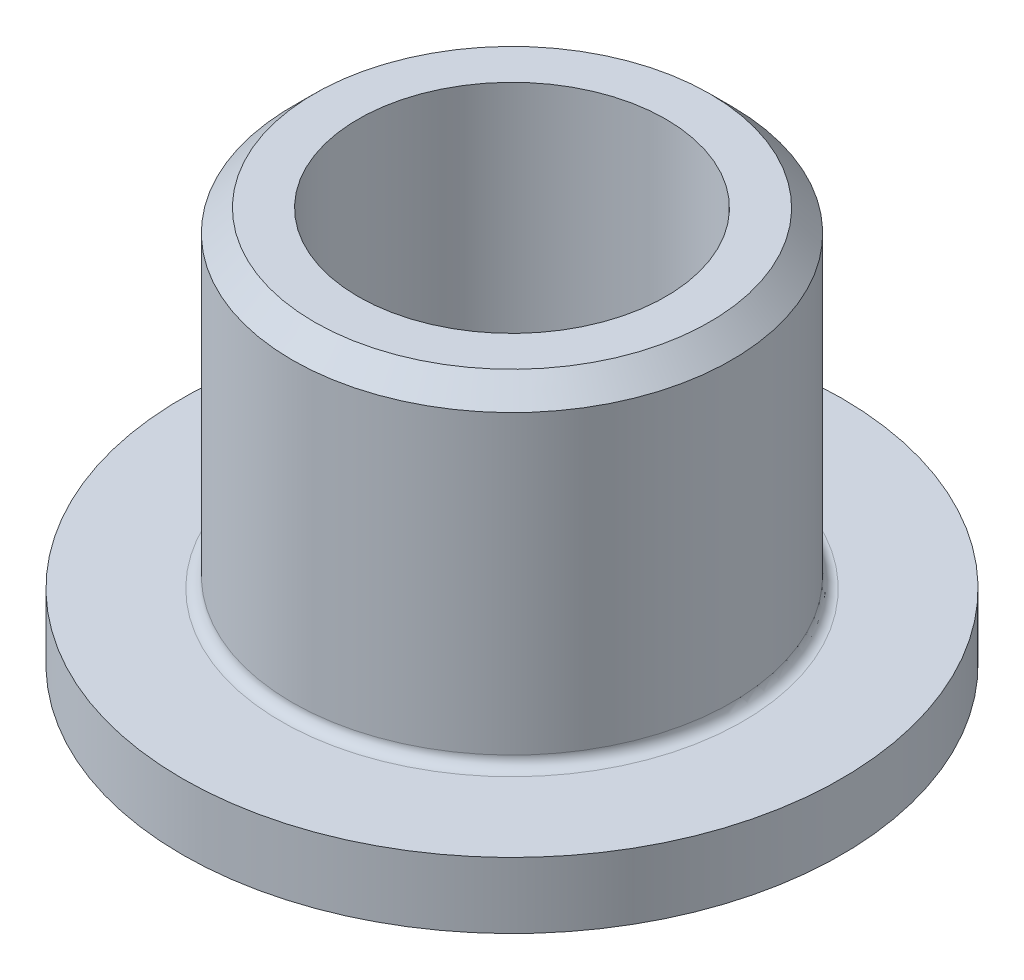
SolidWorks part; units mm, degrees
material "PTFE (general)"
ref_plane "Front Plane" through (0, 0, 0) normal (0, 0, 1) x (1, 0, 0)
ref_plane "Top Plane" through (0, 0, 0) normal (0, 1, 0) x (1, 0, 0)
ref_plane "Right Plane" through (0, 0, 0) normal (1, 0, 0) x (0, 0, -1)
sketch "Sketch1" plane through (0, 0, 0) normal (0, 1, 0) x (1, 0, 0)
  circle A0 centre (0, 0) radius 3.5
  circle A1 centre (0, 0) radius 5
  dimension "D1" = 7
  dimension "D2" = 1.5
extrude "Boss-Extrude1" add sketch "Sketch1" along normal blind 7.5
sketch "Sketch2" plane through (0, 0, 0) normal (0, -1, 0) x (1, 0, 0)
  circle A0 centre (0, 0) radius 3.5 construction
  circle A1 centre (0, 0) radius 3.5
  circle A2 centre (0, 0) radius 5 construction
  circle A3 centre (0, 0) radius 5 construction
  circle A4 centre (0, 0) radius 7.5
  dimension "D1" = 2.5
extrude "Boss-Extrude2" add sketch "Sketch2" along normal blind 1.5
chamfer "Chamfer1" distance 0.5 angle 45 1 edges at (0, 7.5, 5)
fillet "Fillet1" radius 0.25 1 edges at (0, 0, 5)
